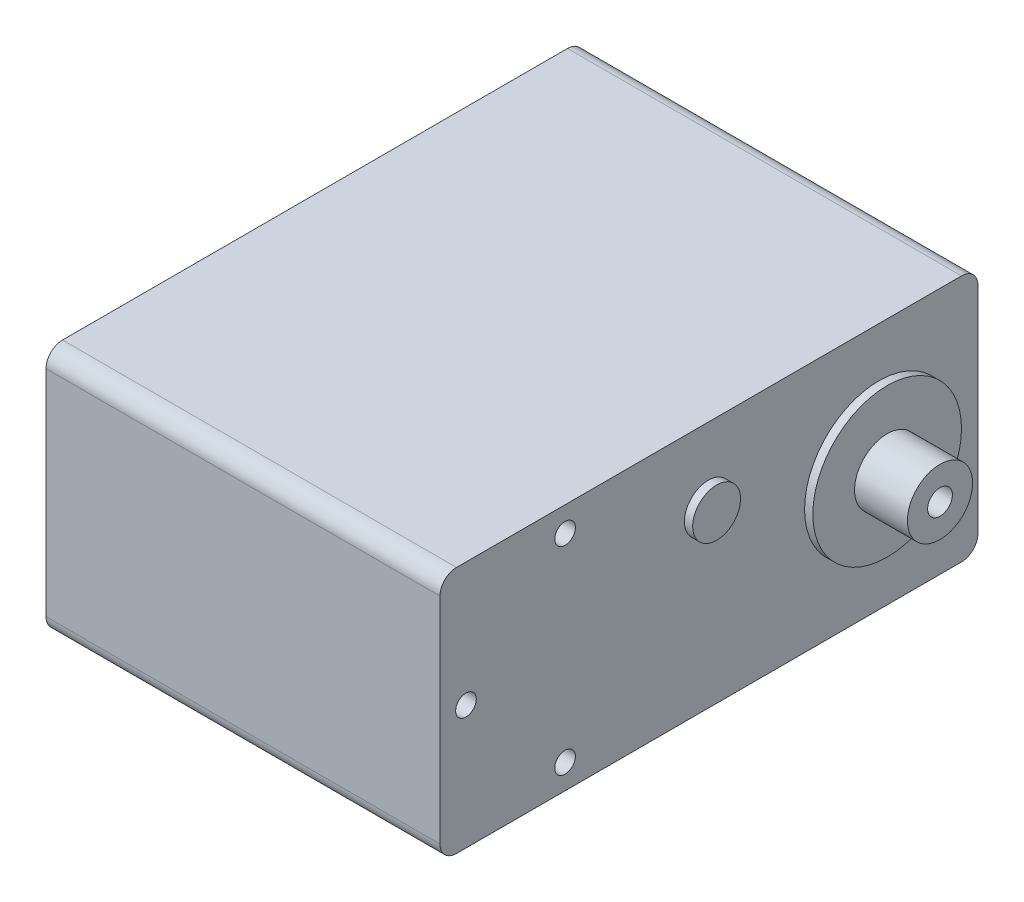
SolidWorks part; units mm, degrees
ref_plane "Plan de face" through (0, 0, 0) normal (0, 0, 1) x (1, 0, 0)
ref_plane "Plan de dessus" through (0, 0, 0) normal (0, 1, 0) x (1, 0, 0)
ref_plane "Plan de droite" through (0, 0, 0) normal (1, 0, 0) x (0, 0, -1)
sketch "Esquisse1" plane through (0, 0, 0) normal (0, 1, 0) x (1, 0, 0)
  line L0 (-23.85, -32.575) -> (23.85, 32.575) construction
  line L1 (-23.85, 32.575) -> (23.85, 32.575)
  line L2 (-23.85, 32.575) -> (-23.85, -32.575)
  line L3 (-23.85, -32.575) -> (23.85, -32.575)
  line L4 (23.85, 32.575) -> (23.85, -32.575)
  point P4 (0, 0)
  dimension "D1" = 65.15
  dimension "D2" = 47.7
extrude "Boss.-Extru.1" add sketch "Esquisse1" along normal mid plane 30
ref_plane "Plan1" through (0, 0, -20.575) normal (0, 0, -1) x (-1, 0, 0)
ref_axis "Axe1" through (42.1187, 0, -20.575) along (-1, 0, 0)
sketch "Esquisse2" plane through (23.85, 0, 0) normal (1, 0, 0) x (0, 0, -1)
  circle A0 centre (20.575, 0) radius 9
  dimension "D1" = 18
extrude "Boss.-Extru.2" add sketch "Esquisse2" along normal blind 1
mirror "Symétrie1" about plane through (0, 0, 0) normal (1, 0, 0) of "Boss.-Extru.2"
sketch "Esquisse3" plane through (24.85, 0, 0) normal (1, 0, 0) x (0, 0, -1)
  circle A0 centre (20.575, 0) radius 3.95
  dimension "D1" = 7.9
extrude "Boss.-Extru.3" add sketch "Esquisse3" along normal blind 6.4
sketch "Esquisse4" plane through (-24.85, 0, 0) normal (-1, 0, 0) x (0, 0, 1)
  circle A0 centre (-20.575, 0) radius 4
  dimension "D1" = 8
extrude "Boss.-Extru.4" add sketch "Esquisse4" along normal blind 0.5
sketch "Esquisse5" plane through (-25.35, 0, 0) normal (-1, 0, 0) x (0, 0, 1)
  circle A0 centre (-20.575, 0) radius 3
  dimension "D1" = 6
extrude "Boss.-Extru.5" add sketch "Esquisse5" along normal blind 5.5
sketch "Esquisse6" plane through (23.85, 0, 0) normal (1, 0, 0) x (0, 0, -1)
  line L0 (-32.575, 15) -> (-32.575, -15) construction
  line L1 (-32.575, 15) -> (32.575, 15) construction
  circle A0 centre (-0.075, 6) radius 2.9
  dimension "D1" = 5.8
  dimension "D2" = 32.5
  dimension "D3" = 9
extrude "Boss.-Extru.6" add sketch "Esquisse6" along normal blind 1
sketch "Esquisse7" plane through (0, 0, -32.575) normal (0, 0, -1) x (-1, 0, 0)
  line L0 (-42.1187, 0) -> (39.7288, 0) construction
  line L1 (17.45, -3.45) -> (13.05, -3.45)
  line L2 (17.45, -3.45) -> (17.45, 3.45)
  line L3 (17.45, 3.45) -> (13.05, 3.45)
  line L4 (13.05, -3.45) -> (13.05, 3.45)
  line L5 (23.85, 15) -> (23.85, -15) construction
  point P4 (17.45, 0)
  dimension "D1" = 6.9
  dimension "D2" = 4.4
  dimension "D3" = 6.4
extrude "Boss.-Extru.7" add sketch "Esquisse7" along normal blind 3.8
sketch "Esquisse8" plane through (0, 0, -36.375) normal (0, 0, -1) x (-1, 0, 0)
  line L1 (17.45, -3.45) -> (17.45, 3.45) construction
  line L2 (13.05, 0) -> (17.45, 0) construction
  line L3 (13.05, 3.45) -> (13.05, -3.45) construction
  line L4 (15.25, 0) -> (15.25, -1.6) construction
  circle A0 centre (15.25, 0) radius 0.75
  circle A1 centre (15.25, -1.6) radius 0.75
  circle A2 centre (15.25, 1.6) radius 0.75
  point P9 (15.25, 0)
  dimension "D1" = 1.5
  dimension "D2" = 1.6
extrude "Boss.-Extru.8" add sketch "Esquisse8" along normal blind 5
hole_wizard "Diamètre du perçage Ø3.0 (3)1" positions "Esquisse9" profile "Esquisse11" hole size "Ø3.0" standard "DIN"
sketch "Esquisse9" plane through (31.25, 0, 0) normal (1, 0, 0) x (0, 0, -1)
  point P0 (20.575, 0)
sketch "Esquisse11" plane through (31.25, 0, -20.575) normal (0, 1, 0) x (0, 0, -1)
  line L0 (0, 0) -> (0, 7.1013)
  line L1 (0, 7.1013) -> (1.5, 6.2)
  line L2 (1.5, 6.2) -> (1.5, 0)
  line L5 (1.5, 0) -> (0, 0)
  line L10 (0, 7.1013) -> (-1.5, 6.2) construction
  line L11 (0, -6.35) -> (0, 107.95) construction
  dimension "Diamètre du perçage" = 3
  dimension "Profondeur du perçage" = 6.2
  dimension "Angle de pointe" = 118
hole_wizard "Diamètre du perçage Ø2.5 (2.5)1" positions "Esquisse12" profile "Esquisse13" hole size "Ø2.5" standard "ISO"
sketch "Esquisse12" plane through (23.85, 0, 0) normal (1, 0, 0) x (0, 0, -1)
  line L2 (-32.575, 15) -> (-32.575, -15) construction
  line L3 (0, 0) -> (-32.575, 0) construction
  line L5 (-17.425, 0) -> (-17.425, 12) construction
  circle A2 centre (-17.425, 0) radius 12 construction
  point P0 (-29.425, 0)
  point P2 (-17.425, 12)
  point P36 (-17.425, -12)
  dimension "D1" = 24
  dimension "D2" = 38
sketch "Esquisse13" plane through (23.85, 0, 29.425) normal (0, 1, 0) x (0, 0, -1)
  line L0 (0, 0) -> (0, 6.9511)
  line L1 (0, 6.9511) -> (1.25, 6.2)
  line L2 (1.25, 6.2) -> (1.25, 0)
  line L5 (1.25, 0) -> (0, 0)
  line L10 (0, 6.9511) -> (-1.25, 6.2) construction
  line L11 (0, -6.35) -> (0, 107.95) construction
  dimension "Diamètre du perçage" = 2.5
  dimension "Profondeur du perçage" = 6.2
  dimension "Angle de pointe" = 118
hole_wizard "Diamètre du perçage Ø2.5 (2.5)2" positions "Esquisse14" profile "Esquisse15" hole size "Ø2.5" standard "DIN"
sketch "Esquisse14" plane through (-23.85, 0, 0) normal (-1, 0, 0) x (0, 0, 1)
  line L0 (-32.575, 0) -> (32.575, 0) construction
  line L1 (-32.575, 15) -> (-32.575, -15) construction
  line L2 (32.575, 15) -> (32.575, -15) construction
  line L4 (0, 0) -> (0, 15) construction
  line L5 (-32.575, 15) -> (32.575, 15) construction
  line L6 (29.5, 12) -> (5.5, 12) construction
  point P6 (29.5, 12)
  point P28 (-29.5, 12)
  point P30 (29.5, -12)
  point P31 (-29.5, -12)
  point P32 (5.5, 12)
  point P38 (5.5, -12)
  dimension "D1" = 24
  dimension "D2" = 59
  dimension "D3" = 24
sketch "Esquisse15" plane through (-23.85, 12, 29.5) normal (0, 1, 0) x (0, 0, 1)
  line L0 (0, 0) -> (0, 6.9511)
  line L1 (0, 6.9511) -> (1.25, 6.2)
  line L2 (1.25, 6.2) -> (1.25, 0)
  line L5 (1.25, 0) -> (0, 0)
  line L10 (0, 6.9511) -> (-1.25, 6.2) construction
  line L11 (0, -6.35) -> (0, 107.95) construction
  dimension "Diamètre du perçage" = 2.5
  dimension "Profondeur du perçage" = 6.2
  dimension "Angle de pointe" = 118
fillet "Congé1" radius 2 4 edges at (0, 15, 32.575) (0, -15, 32.575) (0, 15, -32.575) (0, -15, -32.575)
equation "\"D2@Esquisse8\"=\"D1@Esquisse8\"+0.1"
